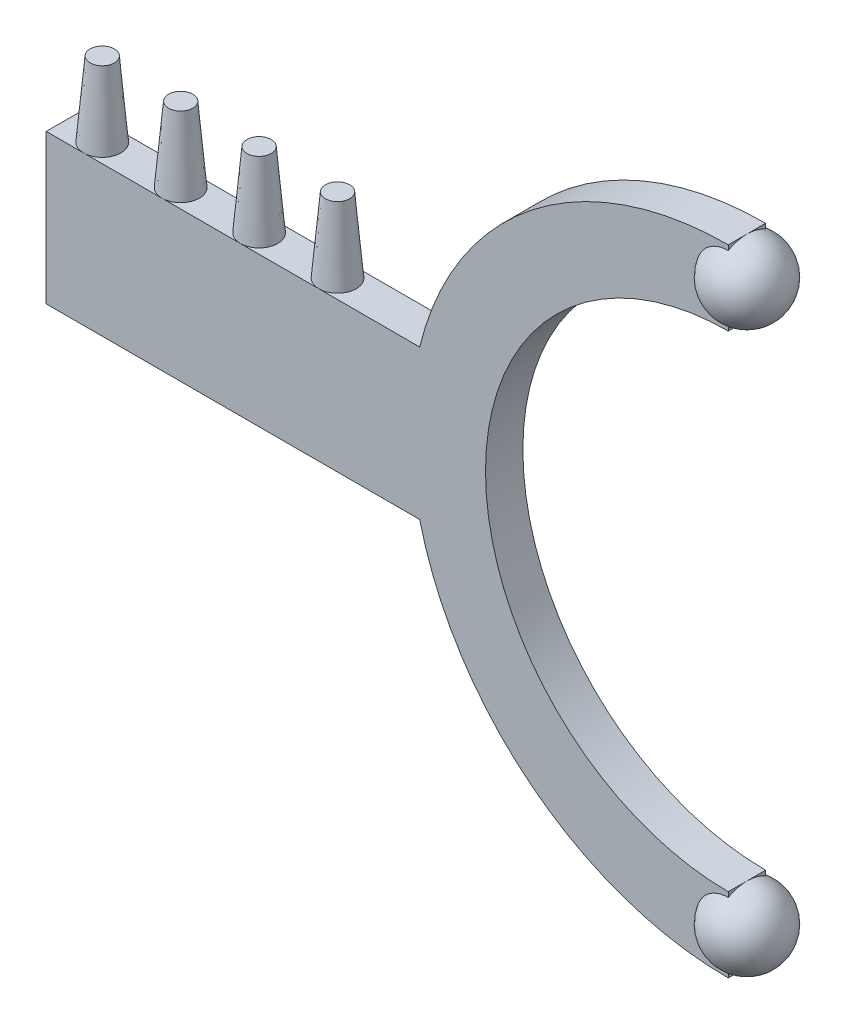
SolidWorks part; units mm, degrees
ref_plane "Front Plane" through (0, 0, 0) normal (0, 0, 1) x (1, 0, 0)
ref_plane "Top Plane" through (0, 0, 0) normal (0, 1, 0) x (1, 0, 0)
ref_plane "Right Plane" through (0, 0, 0) normal (1, 0, 0) x (0, 0, -1)
sketch "Sketch1" plane through (0, 0, 0) normal (0, 0, 1) x (1, 0, 0)
  line L0 (-18.2614, 2) -> (-18.2614, -2)
  line L1 (-8.2614, 2) -> (-18.2614, 2)
  line L2 (-8.2614, -2) -> (-18.2614, -2)
  line L4 (0, -6.5) -> (0, -8.5)
  line L5 (0, 8.5) -> (0, 6.5)
  line L6 (0, 0) -> (0, 2.8656) construction
  arc A0 (0, 6.5) -> (0, -6.5) centre (0, 0) ccw
  arc A1 (0, 8.5) -> (0, -8.5) centre (0, 0) ccw
  arc A4 (0, 8.5) -> (0, 6.5) centre (0, 7.5) ccw
  arc A5 (0, -6.5) -> (0, -8.5) centre (0, -7.5) ccw
  point P5 (-6.5, 0)
  point P11 (-18.2614, 0)
  point P12 (-8.5, 0)
  dimension "D1" = 6.5
  dimension "D2" = 8.5
  dimension "D3" = 2
  dimension "D5" = 4
  dimension "D6" = 10
extrude "Boss-Extrude1" add sketch "Sketch1" along normal mid plane 1 contours A1 L1 L0 L2 | L5 A1 L4 A0 | L5 A4 | L4 A5 region at (-13.3409, 0, 0) region at (-5.1384, 6.5308, 0) region at (-0.4244, 7.5, 0) region at (-0.4244, -7.5, 0)
revolve "Revolve14" add sketch "Sketch1<7>" angle 360 about L6 region at (-0.4244, 7.5, 0) region at (-0.4244, -7.5, 0)
sketch "Sketch1<7>" plane through (0, 0, 0) normal (0, 0, 1) x (1, 0, 0) same geometry as "Sketch1"
sketch "Sketch2" plane through (0, 2, 0) normal (0, 1, 0) x (1, 0, 0)
  line L0 (-18.2614, -0.5) -> (-18.2614, 0.5) construction
  line L1 (-8.2614, -0.5) -> (-8.2614, 0.5) construction
  circle A0 centre (-17.2614, 0) radius 0.5
  circle A1 centre (-15.1614, 0) radius 0.5
  circle A2 centre (-13.0614, 0) radius 0.5
  circle A3 centre (-10.9614, 0) radius 0.5
  point P4 (-18.2614, 0)
  dimension "D1" = 1
  dimension "D2" = 1
  dimension "D3" = 4
  dimension "D4" = 9
extrude "Boss-Extrude2" add sketch "Sketch2" along normal blind 2 draft 5
